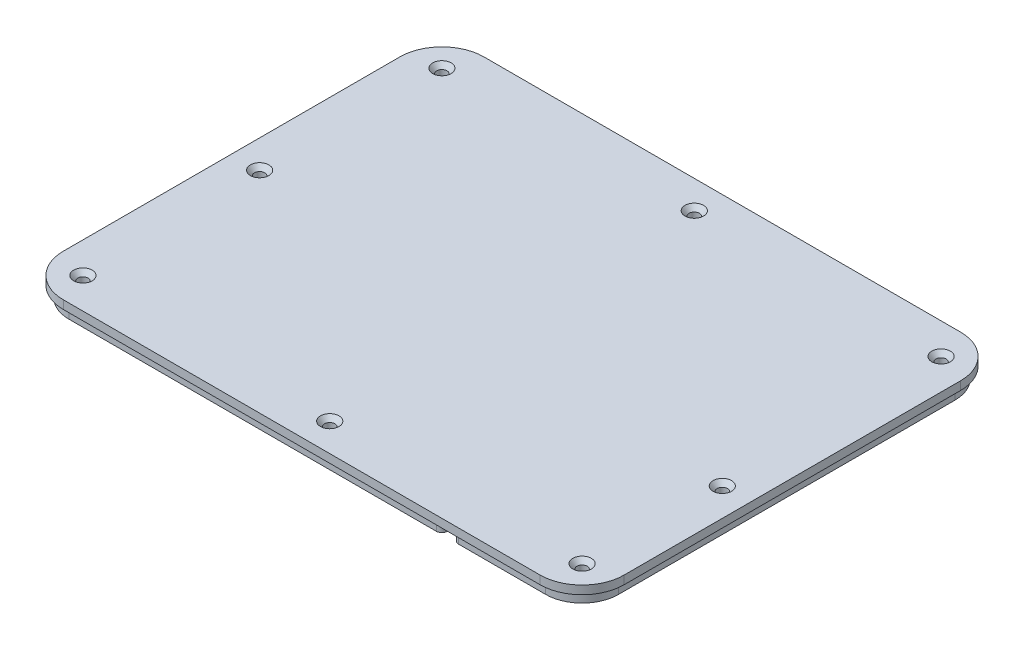
SolidWorks part; units mm, degrees
material "ColorFabb woodFILL"
ref_plane "Front Plane" through (0, 0, 0) normal (0, 0, 1) x (1, 0, 0)
ref_plane "Top Plane" through (0, 0, 0) normal (0, 1, 0) x (1, 0, 0)
ref_plane "Right Plane" through (0, 0, 0) normal (1, 0, 0) x (0, 0, -1)
sketch "BasePlate" plane through (0, 0, 0) normal (0, 1, 0) x (1, 0, 0)
  line L0 (90, -10) -> (94, -10)
  line L1 (-85, 75) -> (85, 75)
  line L2 (-100, 60) -> (-100, -60)
  line L3 (-85, -75) -> (85, -75)
  line L4 (100, 60) -> (100, -60)
  line L5 (88, 60) -> (94, 60)
  line L6 (90, -20) -> (94, -20)
  line L7 (92, 56) -> (62, 56)
  line L8 (-94, 54) -> (-94, 9)
  line L9 (-79, -69) -> (-9, -69)
  line L10 (92, 56) -> (92, 40)
  line L11 (-79, 69) -> (-9, 69)
  line L12 (-94, -9) -> (-94, -54)
  line L13 (9, 69) -> (79, 69)
  line L14 (92, 40) -> (62, 40)
  line L15 (62, 56) -> (62, 40)
  line L16 (9, -69) -> (79, -69)
  line L17 (98, 4) -> (88, 4)
  line L18 (88, -60) -> (94, -60)
  line L19 (88, -59) -> (94, -59)
  line L20 (98, 29) -> (88, 29)
  line L21 (88, 4) -> (88, 29)
  line L22 (98, -54) -> (84, -54)
  line L23 (98, -45) -> (84, -45)
  line L24 (84, -54) -> (84, -45)
  line L25 (98, -27) -> (93, -27)
  line L26 (98, -34.5) -> (93, -34.5)
  line L27 (-85, 73) -> (46, 73)
  line L28 (54, 73) -> (85, 73)
  line L29 (98, 60) -> (98, -60)
  line L30 (54, -73) -> (85, -73)
  line L31 (-85, -73) -> (46, -73)
  line L32 (-98, 60) -> (-98, -60)
  line L33 (93, -27) -> (93, -34.5)
  line L34 (9, -68) -> (79, -68)
  line L35 (-79, -68) -> (-9, -68)
  line L36 (-93, -9) -> (-93, -54)
  line L37 (-93, 54) -> (-93, 9)
  line L38 (-79, 68) -> (-9, 68)
  line L39 (9, 68) -> (79, 68)
  line L40 (88, 59) -> (94, 59)
  line L41 (90, -9) -> (94, -9)
  line L42 (90, -21) -> (94, -21)
  line L43 (97, -56) -> (97, -24)
  line L44 (97, 56) -> (97, -6)
  arc A0 (85, 75) -> (100, 60) centre (85, 60) cw
  arc A1 (85, -75) -> (100, -60) centre (85, -60) ccw
  arc A2 (-100, -60) -> (-85, -75) centre (-85, -60) ccw
  arc A3 (-85, 75) -> (-100, 60) centre (-85, 60) ccw
  arc A4 (94, 60) -> (98, 56) centre (94, 56) cw
  arc A5 (94, -10) -> (98, -6) centre (94, -6) ccw
  arc A6 (48, 71) -> (52, 71) centre (50, 71) ccw
  arc A7 (48, 71) -> (46, 73) centre (46, 71) ccw
  circle A8 centre (55, 0) radius 5
  circle A9 centre (55, 0) radius 25
  circle A10 centre (-55, 0) radius 15
  circle A11 centre (55, 0) radius 22
  arc A12 (-90, -5) -> (-90, 5) centre (-90, 0) ccw
  arc A13 (-90, 5) -> (-94, 9) centre (-90, 9) cw
  arc A14 (-90, -5) -> (-94, -9) centre (-90, -9) ccw
  arc A15 (5, 65) -> (-5, 65) centre (0, 65) cw
  arc A16 (-5, 65) -> (-9, 69) centre (-9, 65) ccw
  arc A17 (5, 65) -> (9, 69) centre (9, 65) cw
  arc A18 (-5, -65) -> (5, -65) centre (0, -65) cw
  arc A19 (-5, -65) -> (-9, -69) centre (-9, -65) cw
  arc A20 (5, -65) -> (9, -69) centre (9, -65) ccw
  arc A21 (52, 71) -> (54, 73) centre (54, 71) cw
  arc A22 (94, -20) -> (98, -24) centre (94, -24) cw
  circle A23 centre (90, -15) radius 1.83
  arc A24 (85, 63) -> (88, 60) centre (88, 63) ccw
  arc A25 (85, 63) -> (79, 69) centre (79, 63) ccw
  arc A26 (52, -71) -> (48, -71) centre (50, -71) ccw
  circle A27 centre (-89, 64) radius 1.83
  arc A28 (-85, 63) -> (-88, 60) centre (-88, 63) cw
  arc A29 (-88, 60) -> (-94, 54) centre (-88, 54) ccw
  arc A30 (-85, 63) -> (-79, 69) centre (-79, 63) cw
  circle A31 centre (89, 64) radius 1.83
  arc A32 (85, -63) -> (79, -69) centre (79, -63) cw
  arc A33 (85, -63) -> (88, -60) centre (88, -63) cw
  arc A34 (94, -60) -> (98, -56) centre (94, -56) ccw
  circle A35 centre (89, -64) radius 1.83
  arc A36 (-88, -60) -> (-85, -63) centre (-88, -63) cw
  arc A37 (-85, -63) -> (-79, -69) centre (-79, -63) ccw
  arc A38 (-88, -60) -> (-94, -54) centre (-88, -54) cw
  circle A39 centre (-89, -64) radius 1.83
  circle A40 centre (0, 65) radius 1.83
  circle A41 centre (-90, 0) radius 1.83
  circle A42 centre (0, -65) radius 1.83
  arc A43 (90, -10) -> (90, -20) centre (90, -15) ccw
  arc A44 (48, -71) -> (46, -73) centre (46, -71) cw
  arc A45 (52, -71) -> (54, -73) centre (54, -71) ccw
  circle A46 centre (79, 63) radius 3
  circle A47 centre (79, 63) radius 1.25
  circle A48 centre (92, 34) radius 3
  circle A49 centre (92, 34) radius 1.25
  circle A50 centre (92, -1) radius 3
  circle A51 centre (92, -1) radius 1.25
  circle A52 centre (80, -20) radius 3
  circle A53 centre (80, -20) radius 1.25
  circle A54 centre (79, -63) radius 3
  circle A55 centre (79, -63) radius 1.25
  circle A56 centre (11, -63) radius 3
  circle A57 centre (11, -63) radius 1.25
  circle A58 centre (-11, -63) radius 3
  circle A59 centre (-11, -63) radius 1.25
  arc A60 (94, -59) -> (97, -56) centre (94, -56) ccw
  arc A61 (84, -63) -> (88, -59) centre (88, -63) cw
  arc A62 (84, -63) -> (79, -68) centre (79, -63) cw
  arc A63 (6, -65) -> (9, -68) centre (9, -65) ccw
  circle A64 centre (-11, 63) radius 3
  circle A65 centre (-11, 63) radius 1.25
  circle A66 centre (11, 63) radius 3
  circle A67 centre (11, 63) radius 1.25
  circle A68 centre (-70, 20) radius 3
  circle A69 centre (-40, 20) radius 3
  circle A70 centre (-40, 20) radius 1.25
  circle A71 centre (-70, 20) radius 1.25
  circle A72 centre (-70, -20) radius 3
  circle A73 centre (-70, -20) radius 1.25
  circle A74 centre (-40, -20) radius 3
  circle A75 centre (-40, -20) radius 1.25
  circle A76 centre (20, 20) radius 3
  arc A77 (85, 73) -> (98, 60) centre (85, 60) cw
  arc A78 (85, -73) -> (98, -60) centre (85, -60) ccw
  circle A79 centre (20, -20) radius 3
  circle A80 centre (20, -20) radius 1.25
  circle A81 centre (20, 20) radius 1.25
  arc A82 (-98, -60) -> (-85, -73) centre (-85, -60) ccw
  arc A83 (-85, 73) -> (-98, 60) centre (-85, 60) ccw
  arc A84 (-6, -65) -> (6, -65) centre (0, -65) cw
  arc A85 (-6, -65) -> (-9, -68) centre (-9, -65) cw
  arc A86 (-84, -63) -> (-79, -68) centre (-79, -63) ccw
  arc A87 (-88, -59) -> (-84, -63) centre (-88, -63) cw
  arc A88 (-88, -59) -> (-93, -54) centre (-88, -54) cw
  arc A89 (-90, -6) -> (-93, -9) centre (-90, -9) ccw
  arc A90 (-90, -6) -> (-90, 6) centre (-90, 0) ccw
  arc A91 (-90, 6) -> (-93, 9) centre (-90, 9) cw
  arc A92 (-88, 59) -> (-93, 54) centre (-88, 54) ccw
  arc A93 (-84, 63) -> (-88, 59) centre (-88, 63) cw
  arc A94 (-84, 63) -> (-79, 68) centre (-79, 63) cw
  arc A95 (-6, 65) -> (-9, 68) centre (-9, 65) ccw
  arc A96 (6, 65) -> (-6, 65) centre (0, 65) cw
  arc A97 (6, 65) -> (9, 68) centre (9, 65) cw
  arc A98 (84, 63) -> (79, 68) centre (79, 63) ccw
  arc A99 (84, 63) -> (88, 59) centre (88, 63) ccw
  arc A100 (94, 59) -> (97, 56) centre (94, 56) cw
  arc A101 (94, -9) -> (97, -6) centre (94, -6) ccw
  arc A102 (90, -9) -> (90, -21) centre (90, -15) ccw
  arc A103 (94, -21) -> (97, -24) centre (94, -24) cw
  circle A104 centre (-55, 0) radius 35 construction
  circle A105 centre (-55, 0) radius 27.5
  circle A106 centre (-55, 0) radius 22.5
  point P240 (0, 0)
  point P241 (0, 0)
  point P242 (0, 0)
extrude "Base Plate" add sketch "BasePlate" against normal blind 3 contours L2 A2 L3 A1 L4 A0 L1 A3
extrude "Inner Base Profile" add sketch "BasePlate<4>" against normal blind 4 from surface contours A83 L32 A82 L31 A44 A26 A45 L30 A78 L29 A77 L28 A21 A6 A7 L27 starting at face at (0, -3, 0)
sketch "BasePlate<4>" plane through (0, 0, 0) normal (0, 1, 0) x (1, 0, 0) same geometry as "BasePlate"
extrude "Mounting Holes" cut sketch "BasePlate<5>" along normal up to surface (-7 mm away) contours A39 | A41 | A27 | A42 | A35 | A23 | A31 | A40 up to face at (25, -7, 0)
sketch "BasePlate<5>" plane through (0, 0, 0) normal (0, 1, 0) x (1, 0, 0) same geometry as "BasePlate"
chamfer "Countersink" distance 1.7 angle 41 8 edges at (-89, 0, 65.83) (89, 0, -62.17) (90, 0, 16.83) (89, 0, 65.83) (0, 0, 66.83) (0, 0, -63.17) (-89, 0, -62.17) (-90, 0, 1.83) first distance on face at (-89, -7, 65.83) first distance on face at (89, -7, -62.17) first distance on face at (90, -7, 16.83) first distance on face at (89, -7, 65.83) first distance on face at (0, -7, 66.83) first distance on face at (0, -7, -63.17) first distance on face at (-89, -7, -62.17) first distance on face at (-90, -7, 1.83)
